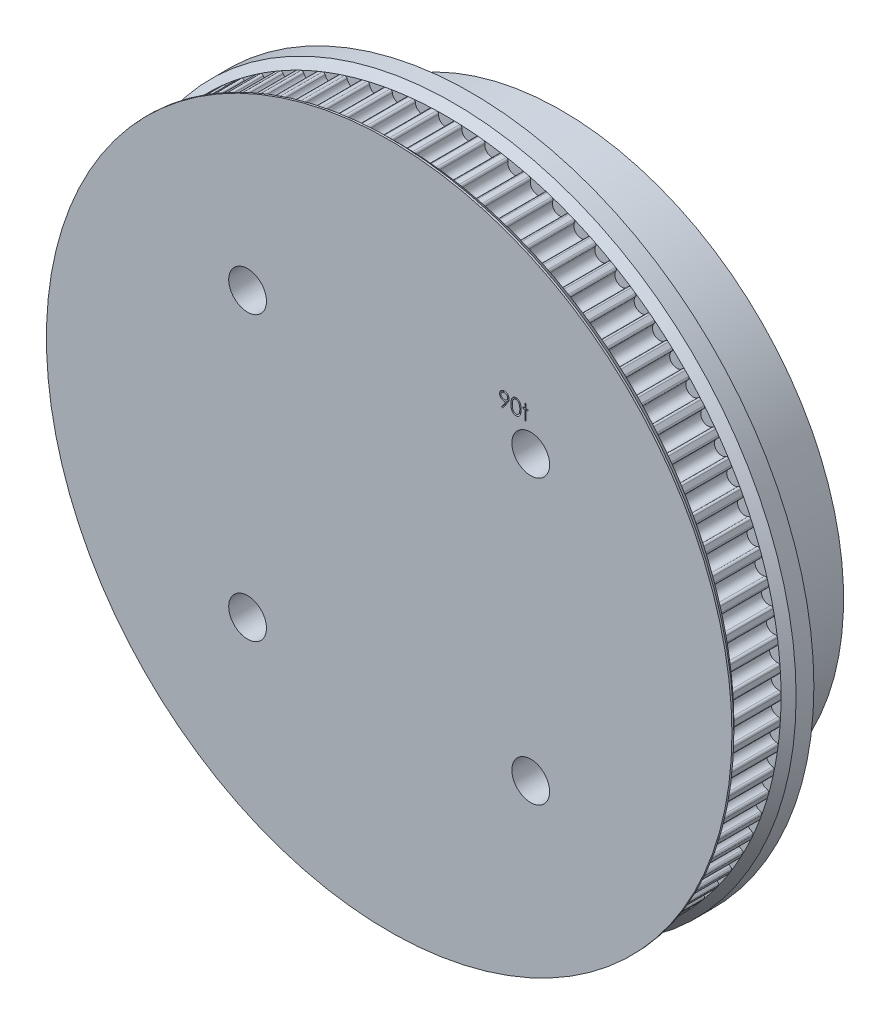
SolidWorks part; units mm, degrees
ref_plane "Front Plane" through (0, 0, 0) normal (0, 0, 1) x (1, 0, 0)
ref_plane "Top Plane" through (0, 0, 0) normal (0, 1, 0) x (1, 0, 0)
ref_plane "Right Plane" through (0, 0, 0) normal (1, 0, 0) x (0, 0, -1)
sketch "Sketch1" plane through (0, 0, 0) normal (0, 0, 1) x (1, 0, 0)
  line L0 (0, 71.6197) -> (0, 0) construction
  line L1 (0, 0) -> (4.9959, 71.4453) construction
  line L2 (0, 70.4947) -> (1.9534, 70.5727) construction
  line L3 (2.9742, 70.537) -> (4.9175, 70.323) construction
  line L4 (1.9534, 70.5727) -> (1.9653, 71.0025) construction
  line L5 (2.9742, 70.537) -> (2.9923, 70.9667) construction
  arc A0 (0, 71.6197) -> (4.9959, 71.4453) centre (0, 0) cw construction
  circle A1 centre (0, 0) radius 71.6197 construction
  circle A2 centre (0, 0) radius 71.0297
  circle A3 centre (0, 0) radius 68.9697
  circle A8 centre (0, 0) radius 72.7697 construction
  circle A9 centre (0, 70.4947) radius 1.525
  circle A10 centre (4.9175, 70.323) radius 1.525
  circle A11 centre (1.9534, 70.5727) radius 0.43
  circle A12 centre (2.9742, 70.537) radius 0.43
  point P18 (0, 68.9697)
  point P19 (4.2572, 15.8881)
  point P20 (4.2572, 15.8881)
  point P21 (1.5238, 70.5555)
  point P23 (3.4016, 70.49)
  dimension "D6" = 3.05
  dimension "D7" = 3.05
  dimension "D8" = 0.86
  dimension "D9" = 0.86
  dimension "D5" = 3.8
  dimension "D2" = 5
  dimension "D3" = 0.59
  dimension "D4" = 2.06
extrude "Boss-Extrude1" add sketch "Sketch1" along normal blind 10 contours A2
extrude "Cut-Extrude1" cut sketch "Sketch1<5>" along normal through all contours A11 A2 A9 | A12 A10 A2 | A9 | A10 region at (3.3605, 70.8449, 0) region at (1.5896, 70.9067, 0)
sketch "Sketch1<5>" plane through (0, 0, 0) normal (0, 0, 1) x (1, 0, 0) same geometry as "Sketch1"
pattern_circular "CirPattern3" count 90 over 360 about axis through (0, 0, 10) along (0, 0, 1) of "Cut-Extrude1"
sketch "Sketch2" plane through (0, 0, 10) normal (0, 0, 1) x (1, 0, 0)
  circle A0 centre (0, 0) radius 72.7697 construction
  arc A81 (-46.5195, 53.0692) -> (-44.1849, 55.0282) centre (-45.3131, 54.0021) ccw
  arc A82 (-46.5195, 53.0692) -> (-44.1849, 55.0282) centre (-45.3131, 54.0021) ccw
  arc A83 (-46.5195, 53.0692) -> (-47.1451, 53.1278) centre (-46.8597, 52.8062) ccw
  arc A84 (-46.5195, 53.0692) -> (-47.1451, 53.1278) centre (-46.8597, 52.8062) ccw
  arc A85 (-47.1451, 53.1278) -> (-47.9088, 52.4402) centre (0, 0) ccw
  arc A86 (-47.1451, 53.1278) -> (-47.9088, 52.4402) centre (0, 0) ccw
  arc A87 (-47.9088, 52.4402) -> (-47.9159, 51.8119) centre (-47.6187, 52.1227) ccw
  arc A88 (-47.9088, 52.4402) -> (-47.9159, 51.8119) centre (-47.6187, 52.1227) ccw
  arc A89 (-50.1081, 49.6949) -> (-47.9159, 51.8119) centre (-48.9698, 50.7097) ccw
  arc A90 (-50.1081, 49.6949) -> (-47.9159, 51.8119) centre (-48.9698, 50.7097) ccw
  arc A91 (-50.1081, 49.6949) -> (-50.7363, 49.7097) centre (-50.4291, 49.4088) ccw
  arc A92 (-50.1081, 49.6949) -> (-50.7363, 49.7097) centre (-50.4291, 49.4088) ccw
  arc A93 (-50.7363, 49.7097) -> (-51.4501, 48.9705) centre (0, 0) ccw
  arc A95 (-50.7363, 49.7097) -> (-51.4501, 48.9705) centre (0, 0) ccw
  arc A97 (-51.4501, 48.9705) -> (-51.4134, 48.3433) centre (-51.1386, 48.674) ccw
  arc A99 (-51.4501, 48.9705) -> (-51.4134, 48.3433) centre (-51.1386, 48.674) ccw
  arc A101 (-53.4526, 46.0785) -> (-51.4134, 48.3433) centre (-52.3878, 47.1702) ccw
  arc A103 (-53.4526, 46.0785) -> (-51.4134, 48.3433) centre (-52.3878, 47.1702) ccw
  arc A105 (-53.4526, 46.0785) -> (-54.0802, 46.0494) centre (-53.7528, 45.7707) ccw
  arc A107 (-53.4526, 46.0785) -> (-54.0802, 46.0494) centre (-53.7528, 45.7707) ccw
  arc A109 (-54.0802, 46.0494) -> (-54.7408, 45.2622) centre (0, 0) ccw
  arc A111 (-54.0802, 46.0494) -> (-54.7408, 45.2622) centre (0, 0) ccw
  arc A112 (-54.7408, 45.2622) -> (-54.6604, 44.6391) centre (-54.4094, 44.9882) ccw
  arc A114 (-54.7408, 45.2622) -> (-54.6604, 44.6391) centre (-54.4094, 44.9882) ccw
  arc A116 (-56.5367, 42.2376) -> (-54.6604, 44.6391) centre (-55.5506, 43.4009) ccw
  arc A118 (-56.5367, 42.2376) -> (-54.6604, 44.6391) centre (-55.5506, 43.4009) ccw
  arc A122 (-56.5367, 42.2376) -> (-57.1607, 42.1648) centre (-56.8147, 41.9096) ccw
  arc A126 (-56.5367, 42.2376) -> (-57.1607, 42.1648) centre (-56.8147, 41.9096) ccw
  arc A130 (-57.1607, 42.1648) -> (-57.7648, 41.3335) centre (0, 0) ccw
  arc A134 (-57.1607, 42.1648) -> (-57.7648, 41.3335) centre (0, 0) ccw
  arc A138 (-57.7648, 41.3335) -> (-57.6411, 40.7174) centre (-57.4151, 41.0832) ccw
  arc A142 (-57.7648, 41.3335) -> (-57.6411, 40.7174) centre (-57.4151, 41.0832) ccw
  arc A146 (-59.3453, 38.1909) -> (-57.6411, 40.7174) centre (-58.4428, 39.4201) ccw
  arc A150 (-59.3453, 38.1909) -> (-57.6411, 40.7174) centre (-58.4428, 39.4201) ccw
  arc A154 (-59.3453, 38.1909) -> (-59.9628, 38.0748) centre (-59.5998, 37.8443) ccw
  arc A158 (-59.3453, 38.1909) -> (-59.9628, 38.0748) centre (-59.5998, 37.8443) ccw
  arc A162 (-59.9628, 38.0748) -> (-60.5073, 37.2033) centre (0, 0) ccw
  arc A166 (-59.9628, 38.0748) -> (-60.5073, 37.2033) centre (0, 0) ccw
  arc A170 (-60.5073, 37.2033) -> (-60.341, 36.5974) centre (-60.141, 36.9781) ccw
  arc A174 (-60.5073, 37.2033) -> (-60.341, 36.5974) centre (-60.141, 36.9781) ccw
  arc A178 (-61.8648, 33.9581) -> (-60.341, 36.5974) centre (-61.0502, 35.2474) ccw
  arc A182 (-61.8648, 33.9581) -> (-60.341, 36.5974) centre (-61.0502, 35.2474) ccw
  arc A186 (-61.8648, 33.9581) -> (-62.4727, 33.7992) centre (-62.0945, 33.5946) ccw
  arc A190 (-61.8648, 33.9581) -> (-62.4727, 33.7992) centre (-62.0945, 33.5946) ccw
  arc A193 (-62.4727, 33.7992) -> (-62.9551, 32.8919) centre (0, 0) ccw
  arc A195 (-62.4727, 33.7992) -> (-62.9551, 32.8919) centre (0, 0) ccw
  arc A197 (-62.9551, 32.8919) -> (-62.7469, 32.2991) centre (-62.574, 32.6928) ccw
  arc A199 (-62.9551, 32.8919) -> (-62.7469, 32.2991) centre (-62.574, 32.6928) ccw
  arc A201 (-64.0829, 29.5599) -> (-62.7469, 32.2991) centre (-63.3602, 30.9029) ccw
  arc A203 (-64.0829, 29.5599) -> (-62.7469, 32.2991) centre (-63.3602, 30.9029) ccw
  arc A205 (-64.0829, 29.5599) -> (-64.6782, 29.359) centre (-64.2867, 29.1813) ccw
  arc A207 (-64.0829, 29.5599) -> (-64.6782, 29.359) centre (-64.2867, 29.1813) ccw
  arc A209 (-64.6782, 29.359) -> (-65.0962, 28.4202) centre (0, 0) ccw
  arc A211 (-64.6782, 29.359) -> (-65.0962, 28.4202) centre (0, 0) ccw
  arc A213 (-65.0962, 28.4202) -> (-64.8471, 27.8434) centre (-64.7021, 28.2482) ccw
  arc A215 (-65.0962, 28.4202) -> (-64.8471, 27.8434) centre (-64.7021, 28.2482) ccw
  arc A217 (-65.9888, 25.0177) -> (-64.8471, 27.8434) centre (-65.3616, 26.4078) ccw
  arc A221 (-65.9888, 25.0177) -> (-64.8471, 27.8434) centre (-65.3616, 26.4078) ccw
  arc A225 (-65.9888, 25.0177) -> (-66.5686, 24.7758) centre (-66.1656, 24.6258) ccw
  arc A229 (-65.9888, 25.0177) -> (-66.5686, 24.7758) centre (-66.1656, 24.6258) ccw
  arc A233 (-66.5686, 24.7758) -> (-66.9201, 23.8101) centre (0, 0) ccw
  arc A241 (-66.5686, 24.7758) -> (-66.9201, 23.8101) centre (0, 0) ccw
  arc A245 (-66.9201, 23.8101) -> (-66.6314, 23.2521) centre (-66.515, 23.666) ccw
  arc A247 (-66.9201, 23.8101) -> (-66.6314, 23.2521) centre (-66.515, 23.666) ccw
  arc A249 (-67.5732, 20.3537) -> (-66.6314, 23.2521) centre (-67.0445, 21.7841) ccw
  arc A251 (-67.5732, 20.3537) -> (-66.6314, 23.2521) centre (-67.0445, 21.7841) ccw
  arc A253 (-67.5732, 20.3537) -> (-68.1347, 20.0718) centre (-67.7223, 19.9503) ccw
  arc A255 (-67.5732, 20.3537) -> (-68.1347, 20.0718) centre (-67.7223, 19.9503) ccw
  arc A257 (-68.1347, 20.0718) -> (-68.418, 19.084) centre (0, 0) ccw
  arc A259 (-68.1347, 20.0718) -> (-68.418, 19.084) centre (0, 0) ccw
  arc A261 (-68.418, 19.084) -> (-68.0911, 18.5475) centre (-68.0038, 18.9685) ccw
  arc A263 (-68.418, 19.084) -> (-68.0911, 18.5475) centre (-68.0038, 18.9685) ccw
  arc A373 (3.4016, 70.49) -> (6.4418, 70.2774) centre (4.9175, 70.323) ccw
  arc A374 (3.4016, 70.49) -> (2.9923, 70.9667) centre (2.9742, 70.537) ccw
  arc A375 (2.9923, 70.9667) -> (1.9653, 71.0025) centre (0, 0) ccw
  arc A376 (1.9653, 71.0025) -> (1.5238, 70.5555) centre (1.9534, 70.5727) ccw
  arc A377 (-1.5238, 70.5555) -> (1.5238, 70.5555) centre (0, 70.4947) ccw
  arc A378 (-1.5238, 70.5555) -> (-1.9653, 71.0025) centre (-1.9534, 70.5727) ccw
  arc A379 (-1.9653, 71.0025) -> (-2.9923, 70.9667) centre (0, 0) ccw
  arc A380 (-2.9923, 70.9667) -> (-3.4016, 70.49) centre (-2.9742, 70.537) ccw
  arc A381 (-6.4418, 70.2774) -> (-3.4016, 70.49) centre (-4.9175, 70.323) ccw
  arc A382 (-6.4418, 70.2774) -> (-6.9134, 70.6925) centre (-6.8716, 70.2645) ccw
  arc A383 (-6.9134, 70.6925) -> (-7.9354, 70.5851) centre (0, 0) ccw
  arc A384 (-7.9354, 70.5851) -> (-8.3105, 70.081) centre (-7.8874, 70.1578) ccw
  arc A385 (-11.3284, 69.6568) -> (-8.3105, 70.081) centre (-9.811, 69.8087) ccw
  arc A386 (-11.3284, 69.6568) -> (-11.8279, 70.038) centre (-11.7563, 69.614) ccw
  arc A387 (-11.8279, 70.038) -> (-12.8399, 69.8596) centre (0, 0) ccw
  arc A388 (-12.8399, 69.8596) -> (-13.1788, 69.3305) centre (-12.7621, 69.4367) ccw
  arc A389 (-16.1598, 68.6969) -> (-13.1788, 69.3305) centre (-14.6567, 68.9542) ccw
  arc A390 (-16.1598, 68.6969) -> (-16.6847, 69.0423) centre (-16.5836, 68.6244) ccw
  arc A391 (-16.6847, 69.0423) -> (-17.6817, 68.7937) centre (0, 0) ccw
  arc A392 (-17.6817, 68.7937) -> (-17.983, 68.2424) centre (-17.5747, 68.3773) ccw
  arc A393 (-20.9125, 67.4023) -> (-17.983, 68.2424) centre (-19.431, 67.7639) ccw
  arc A394 (-20.9125, 67.4023) -> (-21.4602, 67.7103) centre (-21.3302, 67.3004) ccw
  arc A395 (-21.4602, 67.7103) -> (-22.4375, 67.3927) centre (0, 0) ccw
  arc A396 (-22.4375, 67.3927) -> (-22.6995, 66.8217) centre (-22.3016, 66.9848) ccw
  arc A397 (-25.5633, 65.7794) -> (-22.6995, 66.8217) centre (-24.1106, 66.2434) ccw
  arc A398 (-25.5633, 65.7794) -> (-26.1311, 66.0484) centre (-25.9729, 65.6485) ccw
  arc A399 (-26.1311, 66.0484) -> (-27.0839, 65.6634) centre (0, 0) ccw
  arc A400 (-27.0839, 65.6634) -> (-27.3055, 65.0755) centre (-26.9199, 65.2659) ccw
  arc A401 (-30.0896, 63.8359) -> (-27.3055, 65.0755) centre (-28.6728, 64.4001) ccw
  arc A402 (-30.0896, 63.8359) -> (-30.6748, 64.0647) centre (-30.4891, 63.6768) ccw
  arc A403 (-30.6748, 64.0647) -> (-31.5984, 63.6142) centre (0, 0) ccw
  arc A404 (-31.5984, 63.6142) -> (-31.7784, 63.0122) centre (-31.4071, 63.2291) ccw
  arc A405 (-34.4692, 61.5815) -> (-31.7784, 63.0122) centre (-33.0953, 62.2431) ccw
  arc A406 (-34.4692, 61.5815) -> (-35.069, 61.7688) centre (-34.8567, 61.3949) ccw
  arc A407 (-35.069, 61.7688) -> (-35.9589, 61.255) centre (0, 0) ccw
  arc A408 (-35.9589, 61.255) -> (-36.0965, 60.642) centre (-35.7412, 60.8842) ccw
  arc A409 (-38.681, 59.027) -> (-36.0965, 60.642) centre (-37.3565, 59.7829) ccw
  arc A410 (-38.681, 59.027) -> (-39.2923, 59.1721) centre (-39.0544, 58.8139) ccw
  arc A411 (-39.2923, 59.1721) -> (-40.1442, 58.5975) centre (0, 0) ccw
  arc A412 (-40.1442, 58.5975) -> (-40.2387, 57.9763) centre (-39.9012, 58.2427) ccw
  arc A413 (-42.7043, 56.185) -> (-40.2387, 57.9763) centre (-41.4358, 57.0314) ccw
  arc A414 (-42.7043, 56.185) -> (-43.3242, 56.2871) centre (-43.062, 55.9463) ccw
  arc A415 (-43.3242, 56.2871) -> (-44.134, 55.6544) centre (0, 0) ccw
  arc A416 (-44.134, 55.6544) -> (-44.1849, 55.0282) centre (-43.8668, 55.3175) ccw
  arc A649 (3.4016, 70.49) -> (6.4418, 70.2774) centre (4.9175, 70.323) ccw
  arc A650 (3.4016, 70.49) -> (2.9923, 70.9667) centre (2.9742, 70.537) ccw
  arc A651 (2.9923, 70.9667) -> (1.9653, 71.0025) centre (0, 0) ccw
  arc A652 (1.9653, 71.0025) -> (1.5238, 70.5555) centre (1.9534, 70.5727) ccw
  arc A653 (-1.5238, 70.5555) -> (1.5238, 70.5555) centre (0, 70.4947) ccw
  arc A654 (-1.5238, 70.5555) -> (-1.9653, 71.0025) centre (-1.9534, 70.5727) ccw
  arc A655 (-1.9653, 71.0025) -> (-2.9923, 70.9667) centre (0, 0) ccw
  arc A656 (-2.9923, 70.9667) -> (-3.4016, 70.49) centre (-2.9742, 70.537) ccw
  arc A657 (-6.4418, 70.2774) -> (-3.4016, 70.49) centre (-4.9175, 70.323) ccw
  arc A658 (-6.4418, 70.2774) -> (-6.9134, 70.6925) centre (-6.8716, 70.2645) ccw
  arc A659 (-6.9134, 70.6925) -> (-7.9354, 70.5851) centre (0, 0) ccw
  arc A660 (-7.9354, 70.5851) -> (-8.3105, 70.081) centre (-7.8874, 70.1578) ccw
  arc A661 (-11.3284, 69.6568) -> (-8.3105, 70.081) centre (-9.811, 69.8087) ccw
  arc A662 (-11.3284, 69.6568) -> (-11.8279, 70.038) centre (-11.7563, 69.614) ccw
  arc A663 (-11.8279, 70.038) -> (-12.8399, 69.8596) centre (0, 0) ccw
  arc A664 (-12.8399, 69.8596) -> (-13.1788, 69.3305) centre (-12.7621, 69.4367) ccw
  arc A665 (-16.1598, 68.6969) -> (-13.1788, 69.3305) centre (-14.6567, 68.9542) ccw
  arc A666 (-16.1598, 68.6969) -> (-16.6847, 69.0423) centre (-16.5836, 68.6244) ccw
  arc A667 (-16.6847, 69.0423) -> (-17.6817, 68.7937) centre (0, 0) ccw
  arc A668 (-17.6817, 68.7937) -> (-17.983, 68.2424) centre (-17.5747, 68.3773) ccw
  arc A669 (-20.9125, 67.4023) -> (-17.983, 68.2424) centre (-19.431, 67.7639) ccw
  arc A670 (-20.9125, 67.4023) -> (-21.4602, 67.7103) centre (-21.3302, 67.3004) ccw
  arc A671 (-21.4602, 67.7103) -> (-22.4375, 67.3927) centre (0, 0) ccw
  arc A672 (-22.4375, 67.3927) -> (-22.6995, 66.8217) centre (-22.3016, 66.9848) ccw
  arc A673 (-25.5633, 65.7794) -> (-22.6995, 66.8217) centre (-24.1106, 66.2434) ccw
  arc A674 (-25.5633, 65.7794) -> (-26.1311, 66.0484) centre (-25.9729, 65.6485) ccw
  arc A675 (-26.1311, 66.0484) -> (-27.0839, 65.6634) centre (0, 0) ccw
  arc A676 (-27.0839, 65.6634) -> (-27.3055, 65.0755) centre (-26.9199, 65.2659) ccw
  arc A677 (-30.0896, 63.8359) -> (-27.3055, 65.0755) centre (-28.6728, 64.4001) ccw
  arc A678 (-30.0896, 63.8359) -> (-30.6748, 64.0647) centre (-30.4891, 63.6768) ccw
  arc A679 (-30.6748, 64.0647) -> (-31.5984, 63.6142) centre (0, 0) ccw
  arc A680 (-31.5984, 63.6142) -> (-31.7784, 63.0122) centre (-31.4071, 63.2291) ccw
  arc A681 (-34.4692, 61.5815) -> (-31.7784, 63.0122) centre (-33.0953, 62.2431) ccw
  arc A682 (-34.4692, 61.5815) -> (-35.069, 61.7688) centre (-34.8567, 61.3949) ccw
  arc A683 (-35.069, 61.7688) -> (-35.9589, 61.255) centre (0, 0) ccw
  arc A684 (-35.9589, 61.255) -> (-36.0965, 60.642) centre (-35.7412, 60.8842) ccw
  arc A685 (-38.681, 59.027) -> (-36.0965, 60.642) centre (-37.3565, 59.7829) ccw
  arc A686 (-38.681, 59.027) -> (-39.2923, 59.1721) centre (-39.0544, 58.8139) ccw
  arc A687 (-39.2923, 59.1721) -> (-40.1442, 58.5975) centre (0, 0) ccw
  arc A688 (-40.1442, 58.5975) -> (-40.2387, 57.9763) centre (-39.9012, 58.2427) ccw
  arc A689 (-42.7043, 56.185) -> (-40.2387, 57.9763) centre (-41.4358, 57.0314) ccw
  arc A690 (-42.7043, 56.185) -> (-43.3242, 56.2871) centre (-43.062, 55.9463) ccw
  arc A691 (-43.3242, 56.2871) -> (-44.134, 55.6544) centre (0, 0) ccw
  arc A692 (-44.134, 55.6544) -> (-44.1849, 55.0282) centre (-43.8668, 55.3175) ccw
  arc A1359 (-6.9134, -70.6925) -> (-6.4418, -70.2774) centre (-6.8716, -70.2645) ccw
  arc A1361 (-6.9134, -70.6925) -> (-6.4418, -70.2774) centre (-6.8716, -70.2645) ccw
  arc A1363 (-3.4016, -70.49) -> (-6.4418, -70.2774) centre (-4.9175, -70.323) ccw
  arc A1365 (-3.4016, -70.49) -> (-6.4418, -70.2774) centre (-4.9175, -70.323) ccw
  arc A1367 (-3.4016, -70.49) -> (-2.9923, -70.9667) centre (-2.9742, -70.537) ccw
  arc A1369 (-3.4016, -70.49) -> (-2.9923, -70.9667) centre (-2.9742, -70.537) ccw
  arc A1371 (-2.9923, -70.9667) -> (-1.9653, -71.0025) centre (0, 0) ccw
  arc A1373 (-2.9923, -70.9667) -> (-1.9653, -71.0025) centre (0, 0) ccw
  arc A1375 (-1.9653, -71.0025) -> (-1.5238, -70.5555) centre (-1.9534, -70.5727) ccw
  arc A1377 (-1.9653, -71.0025) -> (-1.5238, -70.5555) centre (-1.9534, -70.5727) ccw
  arc A1379 (1.5238, -70.5555) -> (-1.5238, -70.5555) centre (0, -70.4947) ccw
  arc A1381 (1.5238, -70.5555) -> (-1.5238, -70.5555) centre (0, -70.4947) ccw
  arc A1383 (1.5238, -70.5555) -> (1.9653, -71.0025) centre (1.9534, -70.5727) ccw
  arc A1385 (1.5238, -70.5555) -> (1.9653, -71.0025) centre (1.9534, -70.5727) ccw
  arc A1387 (1.9653, -71.0025) -> (2.9923, -70.9667) centre (0, 0) ccw
  arc A1389 (1.9653, -71.0025) -> (2.9923, -70.9667) centre (0, 0) ccw
  arc A1391 (2.9923, -70.9667) -> (3.4016, -70.49) centre (2.9742, -70.537) ccw
  arc A1393 (2.9923, -70.9667) -> (3.4016, -70.49) centre (2.9742, -70.537) ccw
  arc A1395 (6.4418, -70.2774) -> (3.4016, -70.49) centre (4.9175, -70.323) ccw
  arc A1397 (6.4418, -70.2774) -> (3.4016, -70.49) centre (4.9175, -70.323) ccw
  arc A1399 (6.4418, -70.2774) -> (6.9134, -70.6925) centre (6.8716, -70.2645) ccw
  arc A1401 (6.4418, -70.2774) -> (6.9134, -70.6925) centre (6.8716, -70.2645) ccw
  arc A1403 (6.9134, -70.6925) -> (7.9354, -70.5851) centre (0, 0) ccw
  arc A1405 (6.9134, -70.6925) -> (7.9354, -70.5851) centre (0, 0) ccw
  arc A1407 (7.9354, -70.5851) -> (8.3105, -70.081) centre (7.8874, -70.1578) ccw
  arc A1409 (7.9354, -70.5851) -> (8.3105, -70.081) centre (7.8874, -70.1578) ccw
  arc A1411 (11.3284, -69.6568) -> (8.3105, -70.081) centre (9.811, -69.8087) ccw
  arc A1413 (11.3284, -69.6568) -> (8.3105, -70.081) centre (9.811, -69.8087) ccw
  arc A1415 (11.3284, -69.6568) -> (11.8279, -70.038) centre (11.7563, -69.614) ccw
  arc A1417 (11.3284, -69.6568) -> (11.8279, -70.038) centre (11.7563, -69.614) ccw
  arc A1419 (11.8279, -70.038) -> (12.8399, -69.8596) centre (0, 0) ccw
  arc A1421 (11.8279, -70.038) -> (12.8399, -69.8596) centre (0, 0) ccw
  arc A1423 (12.8399, -69.8596) -> (13.1788, -69.3305) centre (12.7621, -69.4367) ccw
  arc A1425 (12.8399, -69.8596) -> (13.1788, -69.3305) centre (12.7621, -69.4367) ccw
  arc A1427 (16.1598, -68.6969) -> (13.1788, -69.3305) centre (14.6567, -68.9542) ccw
  arc A1429 (16.1598, -68.6969) -> (13.1788, -69.3305) centre (14.6567, -68.9542) ccw
  arc A1431 (16.1598, -68.6969) -> (16.6847, -69.0423) centre (16.5836, -68.6244) ccw
  arc A1433 (16.1598, -68.6969) -> (16.6847, -69.0423) centre (16.5836, -68.6244) ccw
  arc A1435 (16.6847, -69.0423) -> (17.6817, -68.7937) centre (0, 0) ccw
  arc A1437 (16.6847, -69.0423) -> (17.6817, -68.7937) centre (0, 0) ccw
  arc A1439 (17.6817, -68.7937) -> (17.983, -68.2424) centre (17.5747, -68.3773) ccw
  arc A1441 (17.6817, -68.7937) -> (17.983, -68.2424) centre (17.5747, -68.3773) ccw
  arc A1443 (20.9125, -67.4023) -> (17.983, -68.2424) centre (19.431, -67.7639) ccw
  arc A1445 (20.9125, -67.4023) -> (17.983, -68.2424) centre (19.431, -67.7639) ccw
  arc A1447 (20.9125, -67.4023) -> (21.4602, -67.7103) centre (21.3302, -67.3004) ccw
  arc A1449 (20.9125, -67.4023) -> (21.4602, -67.7103) centre (21.3302, -67.3004) ccw
  arc A1451 (21.4602, -67.7103) -> (22.4375, -67.3927) centre (0, 0) ccw
  arc A1453 (21.4602, -67.7103) -> (22.4375, -67.3927) centre (0, 0) ccw
  arc A1455 (22.4375, -67.3927) -> (22.6995, -66.8217) centre (22.3016, -66.9848) ccw
  arc A1457 (22.4375, -67.3927) -> (22.6995, -66.8217) centre (22.3016, -66.9848) ccw
  arc A1459 (25.5633, -65.7794) -> (22.6995, -66.8217) centre (24.1106, -66.2434) ccw
  arc A1461 (25.5633, -65.7794) -> (22.6995, -66.8217) centre (24.1106, -66.2434) ccw
  arc A1463 (25.5633, -65.7794) -> (26.1311, -66.0484) centre (25.9729, -65.6485) ccw
  arc A1465 (25.5633, -65.7794) -> (26.1311, -66.0484) centre (25.9729, -65.6485) ccw
  arc A1467 (26.1311, -66.0484) -> (27.0839, -65.6634) centre (0, 0) ccw
  arc A1469 (26.1311, -66.0484) -> (27.0839, -65.6634) centre (0, 0) ccw
  arc A1471 (27.0839, -65.6634) -> (27.3055, -65.0755) centre (26.9199, -65.2659) ccw
  arc A1473 (27.0839, -65.6634) -> (27.3055, -65.0755) centre (26.9199, -65.2659) ccw
  arc A1475 (30.0896, -63.8359) -> (27.3055, -65.0755) centre (28.6728, -64.4001) ccw
  arc A1477 (30.0896, -63.8359) -> (27.3055, -65.0755) centre (28.6728, -64.4001) ccw
  arc A1479 (30.0896, -63.8359) -> (30.6748, -64.0647) centre (30.4891, -63.6768) ccw
  arc A1481 (30.0896, -63.8359) -> (30.6748, -64.0647) centre (30.4891, -63.6768) ccw
  arc A1483 (30.6748, -64.0647) -> (31.5984, -63.6142) centre (0, 0) ccw
  arc A1485 (30.6748, -64.0647) -> (31.5984, -63.6142) centre (0, 0) ccw
  arc A1487 (31.5984, -63.6142) -> (31.7784, -63.0122) centre (31.4071, -63.2291) ccw
  arc A1489 (31.5984, -63.6142) -> (31.7784, -63.0122) centre (31.4071, -63.2291) ccw
  arc A1491 (34.4692, -61.5815) -> (31.7784, -63.0122) centre (33.0953, -62.2431) ccw
  arc A1493 (34.4692, -61.5815) -> (31.7784, -63.0122) centre (33.0953, -62.2431) ccw
  arc A1495 (34.4692, -61.5815) -> (35.069, -61.7688) centre (34.8567, -61.3949) ccw
  arc A1497 (34.4692, -61.5815) -> (35.069, -61.7688) centre (34.8567, -61.3949) ccw
  arc A1499 (35.069, -61.7688) -> (35.9589, -61.255) centre (0, 0) ccw
  arc A1501 (35.069, -61.7688) -> (35.9589, -61.255) centre (0, 0) ccw
  arc A1503 (35.9589, -61.255) -> (36.0965, -60.642) centre (35.7412, -60.8842) ccw
  arc A1505 (35.9589, -61.255) -> (36.0965, -60.642) centre (35.7412, -60.8842) ccw
  arc A1507 (38.681, -59.027) -> (36.0965, -60.642) centre (37.3565, -59.7829) ccw
  arc A1509 (38.681, -59.027) -> (36.0965, -60.642) centre (37.3565, -59.7829) ccw
  arc A1511 (38.681, -59.027) -> (39.2923, -59.1721) centre (39.0544, -58.8139) ccw
  arc A1513 (38.681, -59.027) -> (39.2923, -59.1721) centre (39.0544, -58.8139) ccw
  arc A1515 (39.2923, -59.1721) -> (40.1442, -58.5975) centre (0, 0) ccw
  arc A1517 (39.2923, -59.1721) -> (40.1442, -58.5975) centre (0, 0) ccw
  arc A1519 (40.1442, -58.5975) -> (40.2387, -57.9763) centre (39.9012, -58.2427) ccw
  arc A1521 (40.1442, -58.5975) -> (40.2387, -57.9763) centre (39.9012, -58.2427) ccw
  arc A1523 (42.7043, -56.185) -> (40.2387, -57.9763) centre (41.4358, -57.0314) ccw
  arc A1525 (42.7043, -56.185) -> (40.2387, -57.9763) centre (41.4358, -57.0314) ccw
  arc A1527 (42.7043, -56.185) -> (43.3242, -56.2871) centre (43.062, -55.9463) ccw
  arc A1529 (42.7043, -56.185) -> (43.3242, -56.2871) centre (43.062, -55.9463) ccw
  arc A1531 (43.3242, -56.2871) -> (44.134, -55.6544) centre (0, 0) ccw
  arc A1533 (43.3242, -56.2871) -> (44.134, -55.6544) centre (0, 0) ccw
  arc A1535 (44.134, -55.6544) -> (44.1849, -55.0282) centre (43.8668, -55.3175) ccw
  arc A1537 (44.134, -55.6544) -> (44.1849, -55.0282) centre (43.8668, -55.3175) ccw
  arc A1539 (46.5195, -53.0692) -> (44.1849, -55.0282) centre (45.3131, -54.0021) ccw
  arc A1541 (46.5195, -53.0692) -> (44.1849, -55.0282) centre (45.3131, -54.0021) ccw
  arc A1543 (46.5195, -53.0692) -> (47.1451, -53.1278) centre (46.8597, -52.8062) ccw
  arc A1545 (46.5195, -53.0692) -> (47.1451, -53.1278) centre (46.8597, -52.8062) ccw
  arc A1547 (47.1451, -53.1278) -> (47.9088, -52.4402) centre (0, 0) ccw
  arc A1549 (47.1451, -53.1278) -> (47.9088, -52.4402) centre (0, 0) ccw
  arc A1551 (47.9088, -52.4402) -> (47.9159, -51.8119) centre (47.6187, -52.1227) ccw
  arc A1553 (47.9088, -52.4402) -> (47.9159, -51.8119) centre (47.6187, -52.1227) ccw
  arc A1555 (50.1081, -49.6949) -> (47.9159, -51.8119) centre (48.9698, -50.7097) ccw
  arc A1557 (50.1081, -49.6949) -> (47.9159, -51.8119) centre (48.9698, -50.7097) ccw
  arc A1559 (50.1081, -49.6949) -> (50.7363, -49.7097) centre (50.4291, -49.4088) ccw
  arc A1561 (50.1081, -49.6949) -> (50.7363, -49.7097) centre (50.4291, -49.4088) ccw
  arc A1563 (50.7363, -49.7097) -> (51.4501, -48.9705) centre (0, 0) ccw
  arc A1565 (50.7363, -49.7097) -> (51.4501, -48.9705) centre (0, 0) ccw
  arc A1567 (51.4501, -48.9705) -> (51.4134, -48.3433) centre (51.1386, -48.674) ccw
  arc A1569 (51.4501, -48.9705) -> (51.4134, -48.3433) centre (51.1386, -48.674) ccw
  arc A1571 (53.4526, -46.0785) -> (51.4134, -48.3433) centre (52.3878, -47.1702) ccw
  arc A1573 (53.4526, -46.0785) -> (51.4134, -48.3433) centre (52.3878, -47.1702) ccw
  arc A1575 (53.4526, -46.0785) -> (54.0802, -46.0494) centre (53.7528, -45.7707) ccw
  arc A1577 (53.4526, -46.0785) -> (54.0802, -46.0494) centre (53.7528, -45.7707) ccw
  arc A1579 (54.0802, -46.0494) -> (54.7408, -45.2622) centre (0, 0) ccw
  arc A1581 (54.0802, -46.0494) -> (54.7408, -45.2622) centre (0, 0) ccw
  arc A1583 (54.7408, -45.2622) -> (54.6604, -44.6391) centre (54.4094, -44.9882) ccw
  arc A1585 (54.7408, -45.2622) -> (54.6604, -44.6391) centre (54.4094, -44.9882) ccw
  arc A1587 (56.5367, -42.2376) -> (54.6604, -44.6391) centre (55.5506, -43.4009) ccw
  arc A1589 (56.5367, -42.2376) -> (54.6604, -44.6391) centre (55.5506, -43.4009) ccw
  arc A1591 (56.5367, -42.2376) -> (57.1607, -42.1648) centre (56.8147, -41.9096) ccw
  arc A1593 (56.5367, -42.2376) -> (57.1607, -42.1648) centre (56.8147, -41.9096) ccw
  arc A1595 (57.1607, -42.1648) -> (57.7648, -41.3335) centre (0, 0) ccw
  arc A1596 (57.1607, -42.1648) -> (57.7648, -41.3335) centre (0, 0) ccw
  arc A1597 (57.7648, -41.3335) -> (57.6411, -40.7174) centre (57.4151, -41.0832) ccw
  arc A1598 (57.7648, -41.3335) -> (57.6411, -40.7174) centre (57.4151, -41.0832) ccw
  arc A1599 (59.3453, -38.1909) -> (57.6411, -40.7174) centre (58.4428, -39.4201) ccw
  arc A1600 (59.3453, -38.1909) -> (57.6411, -40.7174) centre (58.4428, -39.4201) ccw
  arc A1601 (59.3453, -38.1909) -> (59.9628, -38.0748) centre (59.5998, -37.8443) ccw
  arc A1602 (59.3453, -38.1909) -> (59.9628, -38.0748) centre (59.5998, -37.8443) ccw
  arc A1603 (59.9628, -38.0748) -> (60.5073, -37.2033) centre (0, 0) ccw
  arc A1604 (59.9628, -38.0748) -> (60.5073, -37.2033) centre (0, 0) ccw
  arc A1605 (60.5073, -37.2033) -> (60.341, -36.5974) centre (60.141, -36.9781) ccw
  arc A1606 (60.5073, -37.2033) -> (60.341, -36.5974) centre (60.141, -36.9781) ccw
  arc A1607 (61.8648, -33.9581) -> (60.341, -36.5974) centre (61.0502, -35.2474) ccw
  arc A1608 (61.8648, -33.9581) -> (60.341, -36.5974) centre (61.0502, -35.2474) ccw
  arc A1609 (61.8648, -33.9581) -> (62.4727, -33.7992) centre (62.0945, -33.5946) ccw
  arc A1610 (61.8648, -33.9581) -> (62.4727, -33.7992) centre (62.0945, -33.5946) ccw
  arc A1611 (62.4727, -33.7992) -> (62.9551, -32.8919) centre (0, 0) ccw
  arc A1612 (62.4727, -33.7992) -> (62.9551, -32.8919) centre (0, 0) ccw
  arc A1613 (62.9551, -32.8919) -> (62.7469, -32.2991) centre (62.574, -32.6928) ccw
  arc A1614 (62.9551, -32.8919) -> (62.7469, -32.2991) centre (62.574, -32.6928) ccw
  arc A1615 (64.0829, -29.5599) -> (62.7469, -32.2991) centre (63.3602, -30.9029) ccw
  arc A1616 (64.0829, -29.5599) -> (62.7469, -32.2991) centre (63.3602, -30.9029) ccw
  arc A1617 (64.0829, -29.5599) -> (64.6782, -29.359) centre (64.2867, -29.1813) ccw
  arc A1618 (64.0829, -29.5599) -> (64.6782, -29.359) centre (64.2867, -29.1813) ccw
  arc A1619 (64.6782, -29.359) -> (65.0962, -28.4202) centre (0, 0) ccw
  arc A1620 (64.6782, -29.359) -> (65.0962, -28.4202) centre (0, 0) ccw
  arc A1621 (65.0962, -28.4202) -> (64.8471, -27.8434) centre (64.7021, -28.2482) ccw
  arc A1622 (65.0962, -28.4202) -> (64.8471, -27.8434) centre (64.7021, -28.2482) ccw
  arc A1623 (65.9888, -25.0177) -> (64.8471, -27.8434) centre (65.3616, -26.4078) ccw
  arc A1624 (65.9888, -25.0177) -> (64.8471, -27.8434) centre (65.3616, -26.4078) ccw
  arc A1625 (65.9888, -25.0177) -> (66.5686, -24.7758) centre (66.1656, -24.6258) ccw
  arc A1626 (65.9888, -25.0177) -> (66.5686, -24.7758) centre (66.1656, -24.6258) ccw
  arc A1627 (66.5686, -24.7758) -> (66.9201, -23.8101) centre (0, 0) ccw
  arc A1628 (66.5686, -24.7758) -> (66.9201, -23.8101) centre (0, 0) ccw
  arc A1629 (66.9201, -23.8101) -> (66.6314, -23.2521) centre (66.515, -23.666) ccw
  arc A1630 (66.9201, -23.8101) -> (66.6314, -23.2521) centre (66.515, -23.666) ccw
  arc A1631 (67.5732, -20.3537) -> (66.6314, -23.2521) centre (67.0445, -21.7841) ccw
  arc A1632 (67.5732, -20.3537) -> (66.6314, -23.2521) centre (67.0445, -21.7841) ccw
  arc A1633 (67.5732, -20.3537) -> (68.1347, -20.0718) centre (67.7223, -19.9503) ccw
  arc A1634 (67.5732, -20.3537) -> (68.1347, -20.0718) centre (67.7223, -19.9503) ccw
  arc A1635 (68.1347, -20.0718) -> (68.418, -19.084) centre (0, 0) ccw
  arc A1636 (68.1347, -20.0718) -> (68.418, -19.084) centre (0, 0) ccw
  arc A1637 (68.418, -19.084) -> (68.0911, -18.5475) centre (68.0038, -18.9685) ccw
  arc A1638 (68.418, -19.084) -> (68.0911, -18.5475) centre (68.0038, -18.9685) ccw
  arc A1639 (68.8284, -15.5904) -> (68.0911, -18.5475) centre (68.4007, -17.0542) ccw
  arc A1640 (68.8284, -15.5904) -> (68.0911, -18.5475) centre (68.4007, -17.0542) ccw
  arc A1641 (68.8284, -15.5904) -> (69.3689, -15.2701) centre (68.949, -15.1777) ccw
  arc A1642 (68.8284, -15.5904) -> (69.3689, -15.2701) centre (68.949, -15.1777) ccw
  arc A1643 (69.3689, -15.2701) -> (69.5826, -14.2649) centre (0, 0) ccw
  arc A1644 (69.3689, -15.2701) -> (69.5826, -14.2649) centre (0, 0) ccw
  arc A1645 (69.5826, -14.2649) -> (69.219, -13.7525) centre (69.1613, -14.1786) ccw
  arc A1646 (69.5826, -14.2649) -> (69.219, -13.7525) centre (69.1613, -14.1786) ccw
  arc A1647 (69.7483, -10.7512) -> (69.219, -13.7525) centre (69.4238, -12.2413) ccw
  arc A1648 (69.7483, -10.7512) -> (69.219, -13.7525) centre (69.4238, -12.2413) ccw
  arc A1649 (69.7483, -10.7512) -> (70.2651, -10.394) centre (69.8397, -10.3311) ccw
  arc A1650 (69.7483, -10.7512) -> (70.2651, -10.394) centre (69.8397, -10.3311) ccw
  arc A1651 (70.2651, -10.394) -> (70.4081, -9.3764) centre (0, 0) ccw
  arc A1652 (70.2651, -10.394) -> (70.4081, -9.3764) centre (0, 0) ccw
  arc A1653 (70.4081, -9.3764) -> (70.0098, -8.8905) centre (69.9819, -9.3196) ccw
  arc A1654 (70.4081, -9.3764) -> (70.0098, -8.8905) centre (69.9819, -9.3196) ccw
  arc A1655 (70.3283, -5.8596) -> (70.0098, -8.8905) centre (70.1085, -7.3687) ccw
  arc A1656 (70.3283, -5.8596) -> (70.0098, -8.8905) centre (70.1085, -7.3687) ccw
  arc A1657 (70.3283, -5.8596) -> (70.819, -5.4672) centre (70.3903, -5.4341) ccw
  arc A1658 (70.3283, -5.8596) -> (70.819, -5.4672) centre (70.3903, -5.4341) ccw
  arc A1659 (70.819, -5.4672) -> (70.8907, -4.4421) centre (0, 0) ccw
  arc A1660 (70.819, -5.4672) -> (70.8907, -4.4421) centre (0, 0) ccw
  arc A1661 (70.8907, -4.4421) -> (70.4594, -3.9852) centre (70.4615, -4.4152) ccw
  arc A1662 (70.8907, -4.4421) -> (70.4594, -3.9852) centre (70.4615, -4.4152) ccw
  arc A1663 (70.5657, -0.9395) -> (70.4594, -3.9852) centre (70.4518, -2.4602) ccw
  arc A1664 (70.5657, -0.9395) -> (70.4594, -3.9852) centre (70.4518, -2.4602) ccw
  arc A1665 (70.5657, -0.9395) -> (71.0279, -0.5138) centre (70.5979, -0.5107) ccw
  arc A1666 (70.5657, -0.9395) -> (71.0279, -0.5138) centre (70.5979, -0.5107) ccw
  arc A1667 (71.0279, -0.5138) -> (71.0279, 0.5138) centre (0, 0) ccw
  arc A1668 (71.0279, -0.5138) -> (71.0279, 0.5138) centre (0, 0) ccw
  arc A1669 (71.0279, 0.5138) -> (70.5657, 0.9395) centre (70.5979, 0.5107) ccw
  arc A1670 (71.0279, 0.5138) -> (70.5657, 0.9395) centre (70.5979, 0.5107) ccw
  arc A1671 (-68.8284, 15.5904) -> (-68.0911, 18.5475) centre (-68.4007, 17.0542) ccw
  arc A1672 (-68.8284, 15.5904) -> (-68.0911, 18.5475) centre (-68.4007, 17.0542) ccw
  arc A1673 (-68.8284, 15.5904) -> (-69.3689, 15.2701) centre (-68.949, 15.1777) ccw
  arc A1674 (-68.8284, 15.5904) -> (-69.3689, 15.2701) centre (-68.949, 15.1777) ccw
  arc A1675 (-69.3689, 15.2701) -> (-69.5826, 14.2649) centre (0, 0) ccw
  arc A1676 (-69.3689, 15.2701) -> (-69.5826, 14.2649) centre (0, 0) ccw
  arc A1677 (-69.5826, 14.2649) -> (-69.219, 13.7525) centre (-69.1613, 14.1786) ccw
  arc A1678 (-69.5826, 14.2649) -> (-69.219, 13.7525) centre (-69.1613, 14.1786) ccw
  arc A1679 (-69.7483, 10.7512) -> (-69.219, 13.7525) centre (-69.4238, 12.2413) ccw
  arc A1680 (-69.7483, 10.7512) -> (-69.219, 13.7525) centre (-69.4238, 12.2413) ccw
  arc A1681 (-69.7483, 10.7512) -> (-70.2651, 10.394) centre (-69.8397, 10.3311) ccw
  arc A1682 (-69.7483, 10.7512) -> (-70.2651, 10.394) centre (-69.8397, 10.3311) ccw
  arc A1683 (-70.2651, 10.394) -> (-70.4081, 9.3764) centre (0, 0) ccw
  arc A1684 (-70.2651, 10.394) -> (-70.4081, 9.3764) centre (0, 0) ccw
  arc A1685 (-70.4081, 9.3764) -> (-70.0098, 8.8905) centre (-69.9819, 9.3196) ccw
  arc A1686 (-70.4081, 9.3764) -> (-70.0098, 8.8905) centre (-69.9819, 9.3196) ccw
  arc A1687 (-70.3283, 5.8596) -> (-70.0098, 8.8905) centre (-70.1085, 7.3687) ccw
  arc A1688 (-70.3283, 5.8596) -> (-70.0098, 8.8905) centre (-70.1085, 7.3687) ccw
  arc A1689 (-70.3283, 5.8596) -> (-70.819, 5.4672) centre (-70.3903, 5.4341) ccw
  arc A1690 (-70.3283, 5.8596) -> (-70.819, 5.4672) centre (-70.3903, 5.4341) ccw
  arc A1691 (-70.819, 5.4672) -> (-70.8907, 4.4421) centre (0, 0) ccw
  arc A1692 (-70.819, 5.4672) -> (-70.8907, 4.4421) centre (0, 0) ccw
  arc A1693 (-70.8907, 4.4421) -> (-70.4594, 3.9852) centre (-70.4615, 4.4152) ccw
  arc A1694 (-70.8907, 4.4421) -> (-70.4594, 3.9852) centre (-70.4615, 4.4152) ccw
  arc A1695 (-70.5657, 0.9395) -> (-70.4594, 3.9852) centre (-70.4518, 2.4602) ccw
  arc A1696 (-70.5657, 0.9395) -> (-70.4594, 3.9852) centre (-70.4518, 2.4602) ccw
  arc A1697 (-70.5657, 0.9395) -> (-71.0279, 0.5138) centre (-70.5979, 0.5107) ccw
  arc A1698 (-70.5657, 0.9395) -> (-71.0279, 0.5138) centre (-70.5979, 0.5107) ccw
  arc A1699 (-71.0279, 0.5138) -> (-71.0279, -0.5138) centre (0, 0) ccw
  arc A1700 (-71.0279, 0.5138) -> (-71.0279, -0.5138) centre (0, 0) ccw
  arc A1701 (-71.0279, -0.5138) -> (-70.5657, -0.9395) centre (-70.5979, -0.5107) ccw
  arc A1702 (-71.0279, -0.5138) -> (-70.5657, -0.9395) centre (-70.5979, -0.5107) ccw
  arc A1703 (-70.4594, -3.9852) -> (-70.5657, -0.9395) centre (-70.4518, -2.4602) ccw
  arc A1704 (-70.4594, -3.9852) -> (-70.5657, -0.9395) centre (-70.4518, -2.4602) ccw
  arc A1705 (-70.4594, -3.9852) -> (-70.8907, -4.4421) centre (-70.4615, -4.4152) ccw
  arc A1706 (-70.4594, -3.9852) -> (-70.8907, -4.4421) centre (-70.4615, -4.4152) ccw
  arc A1707 (-70.8907, -4.4421) -> (-70.819, -5.4672) centre (0, 0) ccw
  arc A1708 (-70.8907, -4.4421) -> (-70.819, -5.4672) centre (0, 0) ccw
  arc A1709 (-70.819, -5.4672) -> (-70.3283, -5.8596) centre (-70.3903, -5.4341) ccw
  arc A1710 (-70.819, -5.4672) -> (-70.3283, -5.8596) centre (-70.3903, -5.4341) ccw
  arc A1711 (-70.0098, -8.8905) -> (-70.3283, -5.8596) centre (-70.1085, -7.3687) ccw
  arc A1712 (-70.0098, -8.8905) -> (-70.3283, -5.8596) centre (-70.1085, -7.3687) ccw
  arc A1713 (-70.0098, -8.8905) -> (-70.4081, -9.3764) centre (-69.9819, -9.3196) ccw
  arc A1714 (-70.0098, -8.8905) -> (-70.4081, -9.3764) centre (-69.9819, -9.3196) ccw
  arc A1715 (-70.4081, -9.3764) -> (-70.2651, -10.394) centre (0, 0) ccw
  arc A1716 (-70.4081, -9.3764) -> (-70.2651, -10.394) centre (0, 0) ccw
  arc A1717 (-70.2651, -10.394) -> (-69.7483, -10.7512) centre (-69.8397, -10.3311) ccw
  arc A1718 (-70.2651, -10.394) -> (-69.7483, -10.7512) centre (-69.8397, -10.3311) ccw
  arc A1719 (-69.219, -13.7525) -> (-69.7483, -10.7512) centre (-69.4238, -12.2413) ccw
  arc A1720 (-69.219, -13.7525) -> (-69.7483, -10.7512) centre (-69.4238, -12.2413) ccw
  arc A1721 (-69.219, -13.7525) -> (-69.5826, -14.2649) centre (-69.1613, -14.1786) ccw
  arc A1722 (-69.219, -13.7525) -> (-69.5826, -14.2649) centre (-69.1613, -14.1786) ccw
  arc A1723 (-69.5826, -14.2649) -> (-69.3689, -15.2701) centre (0, 0) ccw
  arc A1724 (-69.5826, -14.2649) -> (-69.3689, -15.2701) centre (0, 0) ccw
  arc A1725 (-69.3689, -15.2701) -> (-68.8284, -15.5904) centre (-68.949, -15.1777) ccw
  arc A1726 (-69.3689, -15.2701) -> (-68.8284, -15.5904) centre (-68.949, -15.1777) ccw
  arc A1727 (-68.0911, -18.5475) -> (-68.8284, -15.5904) centre (-68.4007, -17.0542) ccw
  arc A1728 (-68.0911, -18.5475) -> (-68.8284, -15.5904) centre (-68.4007, -17.0542) ccw
  arc A1729 (-68.0911, -18.5475) -> (-68.418, -19.084) centre (-68.0038, -18.9685) ccw
  arc A1730 (-68.0911, -18.5475) -> (-68.418, -19.084) centre (-68.0038, -18.9685) ccw
  arc A1731 (-68.418, -19.084) -> (-68.1347, -20.0718) centre (0, 0) ccw
  arc A1732 (-68.418, -19.084) -> (-68.1347, -20.0718) centre (0, 0) ccw
  arc A1733 (-68.1347, -20.0718) -> (-67.5732, -20.3537) centre (-67.7223, -19.9503) ccw
  arc A1734 (-68.1347, -20.0718) -> (-67.5732, -20.3537) centre (-67.7223, -19.9503) ccw
  arc A1735 (-66.6314, -23.2521) -> (-67.5732, -20.3537) centre (-67.0445, -21.7841) ccw
  arc A1736 (-66.6314, -23.2521) -> (-67.5732, -20.3537) centre (-67.0445, -21.7841) ccw
  arc A1737 (-66.6314, -23.2521) -> (-66.9201, -23.8101) centre (-66.515, -23.666) ccw
  arc A1738 (-66.6314, -23.2521) -> (-66.9201, -23.8101) centre (-66.515, -23.666) ccw
  arc A1739 (-66.9201, -23.8101) -> (-66.5686, -24.7758) centre (0, 0) ccw
  arc A1740 (-66.9201, -23.8101) -> (-66.5686, -24.7758) centre (0, 0) ccw
  arc A1741 (-66.5686, -24.7758) -> (-65.9888, -25.0177) centre (-66.1656, -24.6258) ccw
  arc A1742 (-66.5686, -24.7758) -> (-65.9888, -25.0177) centre (-66.1656, -24.6258) ccw
  arc A1743 (-64.8471, -27.8434) -> (-65.9888, -25.0177) centre (-65.3616, -26.4078) ccw
  arc A1744 (-64.8471, -27.8434) -> (-65.9888, -25.0177) centre (-65.3616, -26.4078) ccw
  arc A1745 (-64.8471, -27.8434) -> (-65.0962, -28.4202) centre (-64.7021, -28.2482) ccw
  arc A1746 (-64.8471, -27.8434) -> (-65.0962, -28.4202) centre (-64.7021, -28.2482) ccw
  arc A1747 (-65.0962, -28.4202) -> (-64.6782, -29.359) centre (0, 0) ccw
  arc A1748 (-65.0962, -28.4202) -> (-64.6782, -29.359) centre (0, 0) ccw
  arc A1749 (-64.6782, -29.359) -> (-64.0829, -29.5599) centre (-64.2867, -29.1813) ccw
  arc A1750 (-64.6782, -29.359) -> (-64.0829, -29.5599) centre (-64.2867, -29.1813) ccw
  arc A1751 (-62.7469, -32.2991) -> (-64.0829, -29.5599) centre (-63.3602, -30.9029) ccw
  arc A1752 (-62.7469, -32.2991) -> (-64.0829, -29.5599) centre (-63.3602, -30.9029) ccw
  arc A1753 (-62.7469, -32.2991) -> (-62.9551, -32.8919) centre (-62.574, -32.6928) ccw
  arc A1754 (-62.7469, -32.2991) -> (-62.9551, -32.8919) centre (-62.574, -32.6928) ccw
  arc A1755 (-62.9551, -32.8919) -> (-62.4727, -33.7992) centre (0, 0) ccw
  arc A1756 (-62.9551, -32.8919) -> (-62.4727, -33.7992) centre (0, 0) ccw
  arc A1757 (-62.4727, -33.7992) -> (-61.8648, -33.9581) centre (-62.0945, -33.5946) ccw
  arc A1758 (-62.4727, -33.7992) -> (-61.8648, -33.9581) centre (-62.0945, -33.5946) ccw
  arc A1759 (-60.341, -36.5974) -> (-61.8648, -33.9581) centre (-61.0502, -35.2474) ccw
  arc A1760 (-60.341, -36.5974) -> (-61.8648, -33.9581) centre (-61.0502, -35.2474) ccw
  arc A1761 (-60.341, -36.5974) -> (-60.5073, -37.2033) centre (-60.141, -36.9781) ccw
  arc A1762 (-60.341, -36.5974) -> (-60.5073, -37.2033) centre (-60.141, -36.9781) ccw
  arc A1763 (-60.5073, -37.2033) -> (-59.9628, -38.0748) centre (0, 0) ccw
  arc A1764 (-60.5073, -37.2033) -> (-59.9628, -38.0748) centre (0, 0) ccw
  arc A1765 (-59.9628, -38.0748) -> (-59.3453, -38.1909) centre (-59.5998, -37.8443) ccw
  arc A1766 (-59.9628, -38.0748) -> (-59.3453, -38.1909) centre (-59.5998, -37.8443) ccw
  arc A1767 (-57.6411, -40.7174) -> (-59.3453, -38.1909) centre (-58.4428, -39.4201) ccw
  arc A1768 (-57.6411, -40.7174) -> (-59.3453, -38.1909) centre (-58.4428, -39.4201) ccw
  arc A1769 (-57.6411, -40.7174) -> (-57.7648, -41.3335) centre (-57.4151, -41.0832) ccw
  arc A1770 (-57.6411, -40.7174) -> (-57.7648, -41.3335) centre (-57.4151, -41.0832) ccw
  arc A1771 (-57.7648, -41.3335) -> (-57.1607, -42.1648) centre (0, 0) ccw
  arc A1772 (-57.7648, -41.3335) -> (-57.1607, -42.1648) centre (0, 0) ccw
  arc A1773 (-57.1607, -42.1648) -> (-56.5367, -42.2376) centre (-56.8147, -41.9096) ccw
  arc A1774 (-57.1607, -42.1648) -> (-56.5367, -42.2376) centre (-56.8147, -41.9096) ccw
  arc A1775 (-54.6604, -44.6391) -> (-56.5367, -42.2376) centre (-55.5506, -43.4009) ccw
  arc A1776 (-54.6604, -44.6391) -> (-56.5367, -42.2376) centre (-55.5506, -43.4009) ccw
  arc A1777 (-54.6604, -44.6391) -> (-54.7408, -45.2622) centre (-54.4094, -44.9882) ccw
  arc A1778 (-54.6604, -44.6391) -> (-54.7408, -45.2622) centre (-54.4094, -44.9882) ccw
  arc A1779 (-54.7408, -45.2622) -> (-54.0802, -46.0494) centre (0, 0) ccw
  arc A1780 (-54.7408, -45.2622) -> (-54.0802, -46.0494) centre (0, 0) ccw
  arc A1781 (-54.0802, -46.0494) -> (-53.4526, -46.0785) centre (-53.7528, -45.7707) ccw
  arc A1782 (-54.0802, -46.0494) -> (-53.4526, -46.0785) centre (-53.7528, -45.7707) ccw
  arc A1783 (-51.4134, -48.3433) -> (-53.4526, -46.0785) centre (-52.3878, -47.1702) ccw
  arc A1784 (-51.4134, -48.3433) -> (-53.4526, -46.0785) centre (-52.3878, -47.1702) ccw
  arc A1785 (-51.4134, -48.3433) -> (-51.4501, -48.9705) centre (-51.1386, -48.674) ccw
  arc A1786 (-51.4134, -48.3433) -> (-51.4501, -48.9705) centre (-51.1386, -48.674) ccw
  arc A1787 (-51.4501, -48.9705) -> (-50.7363, -49.7097) centre (0, 0) ccw
  arc A1788 (-51.4501, -48.9705) -> (-50.7363, -49.7097) centre (0, 0) ccw
  arc A1789 (-50.7363, -49.7097) -> (-50.1081, -49.6949) centre (-50.4291, -49.4088) ccw
  arc A1790 (-50.7363, -49.7097) -> (-50.1081, -49.6949) centre (-50.4291, -49.4088) ccw
  arc A1791 (-47.9159, -51.8119) -> (-50.1081, -49.6949) centre (-48.9698, -50.7097) ccw
  arc A1792 (-47.9159, -51.8119) -> (-50.1081, -49.6949) centre (-48.9698, -50.7097) ccw
  arc A1793 (-47.9159, -51.8119) -> (-47.9088, -52.4402) centre (-47.6187, -52.1227) ccw
  arc A1794 (-47.9159, -51.8119) -> (-47.9088, -52.4402) centre (-47.6187, -52.1227) ccw
  arc A1795 (-47.9088, -52.4402) -> (-47.1451, -53.1278) centre (0, 0) ccw
  arc A1796 (-47.9088, -52.4402) -> (-47.1451, -53.1278) centre (0, 0) ccw
  arc A1797 (-47.1451, -53.1278) -> (-46.5195, -53.0692) centre (-46.8597, -52.8062) ccw
  arc A1798 (-47.1451, -53.1278) -> (-46.5195, -53.0692) centre (-46.8597, -52.8062) ccw
  arc A1799 (-44.1849, -55.0282) -> (-46.5195, -53.0692) centre (-45.3131, -54.0021) ccw
  arc A1800 (-44.1849, -55.0282) -> (-46.5195, -53.0692) centre (-45.3131, -54.0021) ccw
  arc A1801 (-44.1849, -55.0282) -> (-44.134, -55.6544) centre (-43.8668, -55.3175) ccw
  arc A1802 (-44.1849, -55.0282) -> (-44.134, -55.6544) centre (-43.8668, -55.3175) ccw
  arc A1803 (-44.134, -55.6544) -> (-43.3242, -56.2871) centre (0, 0) ccw
  arc A1804 (-44.134, -55.6544) -> (-43.3242, -56.2871) centre (0, 0) ccw
  arc A1805 (-43.3242, -56.2871) -> (-42.7043, -56.185) centre (-43.062, -55.9463) ccw
  arc A1806 (-43.3242, -56.2871) -> (-42.7043, -56.185) centre (-43.062, -55.9463) ccw
  arc A1807 (-40.2387, -57.9763) -> (-42.7043, -56.185) centre (-41.4358, -57.0314) ccw
  arc A1808 (-40.2387, -57.9763) -> (-42.7043, -56.185) centre (-41.4358, -57.0314) ccw
  arc A1809 (-40.2387, -57.9763) -> (-40.1442, -58.5975) centre (-39.9012, -58.2427) ccw
  arc A1810 (-40.2387, -57.9763) -> (-40.1442, -58.5975) centre (-39.9012, -58.2427) ccw
  arc A1811 (-40.1442, -58.5975) -> (-39.2923, -59.1721) centre (0, 0) ccw
  arc A1812 (-40.1442, -58.5975) -> (-39.2923, -59.1721) centre (0, 0) ccw
  arc A1813 (-39.2923, -59.1721) -> (-38.681, -59.027) centre (-39.0544, -58.8139) ccw
  arc A1814 (-39.2923, -59.1721) -> (-38.681, -59.027) centre (-39.0544, -58.8139) ccw
  arc A1815 (-36.0965, -60.642) -> (-38.681, -59.027) centre (-37.3565, -59.7829) ccw
  arc A1816 (-36.0965, -60.642) -> (-38.681, -59.027) centre (-37.3565, -59.7829) ccw
  arc A1817 (-36.0965, -60.642) -> (-35.9589, -61.255) centre (-35.7412, -60.8842) ccw
  arc A1818 (-36.0965, -60.642) -> (-35.9589, -61.255) centre (-35.7412, -60.8842) ccw
  arc A1819 (-35.9589, -61.255) -> (-35.069, -61.7688) centre (0, 0) ccw
  arc A1820 (-35.9589, -61.255) -> (-35.069, -61.7688) centre (0, 0) ccw
  arc A1821 (-35.069, -61.7688) -> (-34.4692, -61.5815) centre (-34.8567, -61.3949) ccw
  arc A1822 (-35.069, -61.7688) -> (-34.4692, -61.5815) centre (-34.8567, -61.3949) ccw
  arc A1823 (-31.7784, -63.0122) -> (-34.4692, -61.5815) centre (-33.0953, -62.2431) ccw
  arc A1824 (-31.7784, -63.0122) -> (-34.4692, -61.5815) centre (-33.0953, -62.2431) ccw
  arc A1825 (-31.7784, -63.0122) -> (-31.5984, -63.6142) centre (-31.4071, -63.2291) ccw
  arc A1826 (-31.7784, -63.0122) -> (-31.5984, -63.6142) centre (-31.4071, -63.2291) ccw
  arc A1827 (-31.5984, -63.6142) -> (-30.6748, -64.0647) centre (0, 0) ccw
  arc A1828 (-31.5984, -63.6142) -> (-30.6748, -64.0647) centre (0, 0) ccw
  arc A1829 (-30.6748, -64.0647) -> (-30.0896, -63.8359) centre (-30.4891, -63.6768) ccw
  arc A1830 (-30.6748, -64.0647) -> (-30.0896, -63.8359) centre (-30.4891, -63.6768) ccw
  arc A1831 (-27.3055, -65.0755) -> (-30.0896, -63.8359) centre (-28.6728, -64.4001) ccw
  arc A1832 (-27.3055, -65.0755) -> (-30.0896, -63.8359) centre (-28.6728, -64.4001) ccw
  arc A1833 (-27.3055, -65.0755) -> (-27.0839, -65.6634) centre (-26.9199, -65.2659) ccw
  arc A1834 (-27.3055, -65.0755) -> (-27.0839, -65.6634) centre (-26.9199, -65.2659) ccw
  arc A1835 (-27.0839, -65.6634) -> (-26.1311, -66.0484) centre (0, 0) ccw
  arc A1836 (-27.0839, -65.6634) -> (-26.1311, -66.0484) centre (0, 0) ccw
  arc A1837 (-26.1311, -66.0484) -> (-25.5633, -65.7794) centre (-25.9729, -65.6485) ccw
  arc A1838 (-26.1311, -66.0484) -> (-25.5633, -65.7794) centre (-25.9729, -65.6485) ccw
  arc A1839 (-22.6995, -66.8217) -> (-25.5633, -65.7794) centre (-24.1106, -66.2434) ccw
  arc A1840 (-22.6995, -66.8217) -> (-25.5633, -65.7794) centre (-24.1106, -66.2434) ccw
  arc A1841 (-22.6995, -66.8217) -> (-22.4375, -67.3927) centre (-22.3016, -66.9848) ccw
  arc A1842 (-22.6995, -66.8217) -> (-22.4375, -67.3927) centre (-22.3016, -66.9848) ccw
  arc A1843 (-22.4375, -67.3927) -> (-21.4602, -67.7103) centre (0, 0) ccw
  arc A1844 (-22.4375, -67.3927) -> (-21.4602, -67.7103) centre (0, 0) ccw
  arc A1845 (-21.4602, -67.7103) -> (-20.9125, -67.4023) centre (-21.3302, -67.3004) ccw
  arc A1846 (-21.4602, -67.7103) -> (-20.9125, -67.4023) centre (-21.3302, -67.3004) ccw
  arc A1847 (-17.983, -68.2424) -> (-20.9125, -67.4023) centre (-19.431, -67.7639) ccw
  arc A1848 (-17.983, -68.2424) -> (-20.9125, -67.4023) centre (-19.431, -67.7639) ccw
  arc A1849 (-17.983, -68.2424) -> (-17.6817, -68.7937) centre (-17.5747, -68.3773) ccw
  arc A1850 (-17.983, -68.2424) -> (-17.6817, -68.7937) centre (-17.5747, -68.3773) ccw
  arc A1851 (-17.6817, -68.7937) -> (-16.6847, -69.0423) centre (0, 0) ccw
  arc A1852 (-17.6817, -68.7937) -> (-16.6847, -69.0423) centre (0, 0) ccw
  arc A1853 (-16.6847, -69.0423) -> (-16.1598, -68.6969) centre (-16.5836, -68.6244) ccw
  arc A1854 (-16.6847, -69.0423) -> (-16.1598, -68.6969) centre (-16.5836, -68.6244) ccw
  arc A1855 (-13.1788, -69.3305) -> (-16.1598, -68.6969) centre (-14.6567, -68.9542) ccw
  arc A1856 (-13.1788, -69.3305) -> (-16.1598, -68.6969) centre (-14.6567, -68.9542) ccw
  arc A1857 (-13.1788, -69.3305) -> (-12.8399, -69.8596) centre (-12.7621, -69.4367) ccw
  arc A1858 (-13.1788, -69.3305) -> (-12.8399, -69.8596) centre (-12.7621, -69.4367) ccw
  arc A1859 (-12.8399, -69.8596) -> (-11.8279, -70.038) centre (0, 0) ccw
  arc A1860 (-12.8399, -69.8596) -> (-11.8279, -70.038) centre (0, 0) ccw
  arc A1861 (-11.8279, -70.038) -> (-11.3284, -69.6568) centre (-11.7563, -69.614) ccw
  arc A1862 (-11.8279, -70.038) -> (-11.3284, -69.6568) centre (-11.7563, -69.614) ccw
  arc A1863 (-8.3105, -70.081) -> (-11.3284, -69.6568) centre (-9.811, -69.8087) ccw
  arc A1864 (-8.3105, -70.081) -> (-11.3284, -69.6568) centre (-9.811, -69.8087) ccw
  arc A1865 (-8.3105, -70.081) -> (-7.9354, -70.5851) centre (-7.8874, -70.1578) ccw
  arc A1866 (-8.3105, -70.081) -> (-7.9354, -70.5851) centre (-7.8874, -70.1578) ccw
  arc A1867 (-7.9354, -70.5851) -> (-6.9134, -70.6925) centre (0, 0) ccw
  arc A1868 (-7.9354, -70.5851) -> (-6.9134, -70.6925) centre (0, 0) ccw
  arc A1869 (70.4594, 3.9852) -> (70.5657, 0.9395) centre (70.4518, 2.4602) ccw
  arc A1870 (70.4594, 3.9852) -> (70.5657, 0.9395) centre (70.4518, 2.4602) ccw
  arc A1871 (70.4594, 3.9852) -> (70.8907, 4.4421) centre (70.4615, 4.4152) ccw
  arc A1872 (70.4594, 3.9852) -> (70.8907, 4.4421) centre (70.4615, 4.4152) ccw
  arc A1873 (70.8907, 4.4421) -> (70.819, 5.4672) centre (0, 0) ccw
  arc A1874 (70.8907, 4.4421) -> (70.819, 5.4672) centre (0, 0) ccw
  arc A1875 (70.819, 5.4672) -> (70.3283, 5.8596) centre (70.3903, 5.4341) ccw
  arc A1876 (70.819, 5.4672) -> (70.3283, 5.8596) centre (70.3903, 5.4341) ccw
  arc A1877 (70.0098, 8.8905) -> (70.3283, 5.8596) centre (70.1085, 7.3687) ccw
  arc A1878 (70.0098, 8.8905) -> (70.3283, 5.8596) centre (70.1085, 7.3687) ccw
  arc A1879 (70.0098, 8.8905) -> (70.4081, 9.3764) centre (69.9819, 9.3196) ccw
  arc A1880 (70.0098, 8.8905) -> (70.4081, 9.3764) centre (69.9819, 9.3196) ccw
  arc A1881 (70.4081, 9.3764) -> (70.2651, 10.394) centre (0, 0) ccw
  arc A1882 (70.4081, 9.3764) -> (70.2651, 10.394) centre (0, 0) ccw
  arc A1883 (70.2651, 10.394) -> (69.7483, 10.7512) centre (69.8397, 10.3311) ccw
  arc A1884 (70.2651, 10.394) -> (69.7483, 10.7512) centre (69.8397, 10.3311) ccw
  arc A1885 (69.219, 13.7525) -> (69.7483, 10.7512) centre (69.4238, 12.2413) ccw
  arc A1886 (69.219, 13.7525) -> (69.7483, 10.7512) centre (69.4238, 12.2413) ccw
  arc A1887 (69.219, 13.7525) -> (69.5826, 14.2649) centre (69.1613, 14.1786) ccw
  arc A1888 (69.219, 13.7525) -> (69.5826, 14.2649) centre (69.1613, 14.1786) ccw
  arc A1889 (69.5826, 14.2649) -> (69.3689, 15.2701) centre (0, 0) ccw
  arc A1890 (69.5826, 14.2649) -> (69.3689, 15.2701) centre (0, 0) ccw
  arc A1891 (69.3689, 15.2701) -> (68.8284, 15.5904) centre (68.949, 15.1777) ccw
  arc A1892 (69.3689, 15.2701) -> (68.8284, 15.5904) centre (68.949, 15.1777) ccw
  arc A1893 (68.0911, 18.5475) -> (68.8284, 15.5904) centre (68.4007, 17.0542) ccw
  arc A1894 (68.0911, 18.5475) -> (68.8284, 15.5904) centre (68.4007, 17.0542) ccw
  arc A1895 (68.0911, 18.5475) -> (68.418, 19.084) centre (68.0038, 18.9685) ccw
  arc A1896 (68.0911, 18.5475) -> (68.418, 19.084) centre (68.0038, 18.9685) ccw
  arc A1897 (68.418, 19.084) -> (68.1347, 20.0718) centre (0, 0) ccw
  arc A1898 (68.418, 19.084) -> (68.1347, 20.0718) centre (0, 0) ccw
  arc A1899 (68.1347, 20.0718) -> (67.5732, 20.3537) centre (67.7223, 19.9503) ccw
  arc A1900 (68.1347, 20.0718) -> (67.5732, 20.3537) centre (67.7223, 19.9503) ccw
  arc A1901 (66.6314, 23.2521) -> (67.5732, 20.3537) centre (67.0445, 21.7841) ccw
  arc A1902 (66.6314, 23.2521) -> (67.5732, 20.3537) centre (67.0445, 21.7841) ccw
  arc A1903 (66.6314, 23.2521) -> (66.9201, 23.8101) centre (66.515, 23.666) ccw
  arc A1904 (66.6314, 23.2521) -> (66.9201, 23.8101) centre (66.515, 23.666) ccw
  arc A1905 (66.9201, 23.8101) -> (66.5686, 24.7758) centre (0, 0) ccw
  arc A1906 (66.9201, 23.8101) -> (66.5686, 24.7758) centre (0, 0) ccw
  arc A1907 (66.5686, 24.7758) -> (65.9888, 25.0177) centre (66.1656, 24.6258) ccw
  arc A1908 (66.5686, 24.7758) -> (65.9888, 25.0177) centre (66.1656, 24.6258) ccw
  arc A1909 (64.8471, 27.8434) -> (65.9888, 25.0177) centre (65.3616, 26.4078) ccw
  arc A1910 (64.8471, 27.8434) -> (65.9888, 25.0177) centre (65.3616, 26.4078) ccw
  arc A1911 (64.8471, 27.8434) -> (65.0962, 28.4202) centre (64.7021, 28.2482) ccw
  arc A1912 (64.8471, 27.8434) -> (65.0962, 28.4202) centre (64.7021, 28.2482) ccw
  arc A1913 (65.0962, 28.4202) -> (64.6782, 29.359) centre (0, 0) ccw
  arc A1914 (65.0962, 28.4202) -> (64.6782, 29.359) centre (0, 0) ccw
  arc A1915 (64.6782, 29.359) -> (64.0829, 29.5599) centre (64.2867, 29.1813) ccw
  arc A1916 (64.6782, 29.359) -> (64.0829, 29.5599) centre (64.2867, 29.1813) ccw
  arc A1917 (62.7469, 32.2991) -> (64.0829, 29.5599) centre (63.3602, 30.9029) ccw
  arc A1918 (62.7469, 32.2991) -> (64.0829, 29.5599) centre (63.3602, 30.9029) ccw
  arc A1919 (62.7469, 32.2991) -> (62.9551, 32.8919) centre (62.574, 32.6928) ccw
  arc A1920 (62.7469, 32.2991) -> (62.9551, 32.8919) centre (62.574, 32.6928) ccw
  arc A1921 (62.9551, 32.8919) -> (62.4727, 33.7992) centre (0, 0) ccw
  arc A1922 (62.9551, 32.8919) -> (62.4727, 33.7992) centre (0, 0) ccw
  arc A1923 (62.4727, 33.7992) -> (61.8648, 33.9581) centre (62.0945, 33.5946) ccw
  arc A1924 (62.4727, 33.7992) -> (61.8648, 33.9581) centre (62.0945, 33.5946) ccw
  arc A1925 (60.341, 36.5974) -> (61.8648, 33.9581) centre (61.0502, 35.2474) ccw
  arc A1926 (60.341, 36.5974) -> (61.8648, 33.9581) centre (61.0502, 35.2474) ccw
  arc A1927 (60.341, 36.5974) -> (60.5073, 37.2033) centre (60.141, 36.9781) ccw
  arc A1928 (60.341, 36.5974) -> (60.5073, 37.2033) centre (60.141, 36.9781) ccw
  arc A1929 (60.5073, 37.2033) -> (59.9628, 38.0748) centre (0, 0) ccw
  arc A1930 (60.5073, 37.2033) -> (59.9628, 38.0748) centre (0, 0) ccw
  arc A1931 (59.9628, 38.0748) -> (59.3453, 38.1909) centre (59.5998, 37.8443) ccw
  arc A1932 (59.9628, 38.0748) -> (59.3453, 38.1909) centre (59.5998, 37.8443) ccw
  arc A1933 (57.6411, 40.7174) -> (59.3453, 38.1909) centre (58.4428, 39.4201) ccw
  arc A1934 (57.6411, 40.7174) -> (59.3453, 38.1909) centre (58.4428, 39.4201) ccw
  arc A1935 (57.6411, 40.7174) -> (57.7648, 41.3335) centre (57.4151, 41.0832) ccw
  arc A1936 (57.6411, 40.7174) -> (57.7648, 41.3335) centre (57.4151, 41.0832) ccw
  arc A1937 (57.7648, 41.3335) -> (57.1607, 42.1648) centre (0, 0) ccw
  arc A1938 (57.7648, 41.3335) -> (57.1607, 42.1648) centre (0, 0) ccw
  arc A1939 (57.1607, 42.1648) -> (56.5367, 42.2376) centre (56.8147, 41.9096) ccw
  arc A1940 (57.1607, 42.1648) -> (56.5367, 42.2376) centre (56.8147, 41.9096) ccw
  arc A1941 (54.6604, 44.6391) -> (56.5367, 42.2376) centre (55.5506, 43.4009) ccw
  arc A1942 (54.6604, 44.6391) -> (56.5367, 42.2376) centre (55.5506, 43.4009) ccw
  arc A1943 (54.6604, 44.6391) -> (54.7408, 45.2622) centre (54.4094, 44.9882) ccw
  arc A1944 (54.6604, 44.6391) -> (54.7408, 45.2622) centre (54.4094, 44.9882) ccw
  arc A1945 (54.7408, 45.2622) -> (54.0802, 46.0494) centre (0, 0) ccw
  arc A1946 (54.7408, 45.2622) -> (54.0802, 46.0494) centre (0, 0) ccw
  arc A1947 (54.0802, 46.0494) -> (53.4526, 46.0785) centre (53.7528, 45.7707) ccw
  arc A1948 (54.0802, 46.0494) -> (53.4526, 46.0785) centre (53.7528, 45.7707) ccw
  arc A1949 (51.4134, 48.3433) -> (53.4526, 46.0785) centre (52.3878, 47.1702) ccw
  arc A1950 (51.4134, 48.3433) -> (53.4526, 46.0785) centre (52.3878, 47.1702) ccw
  arc A1951 (51.4134, 48.3433) -> (51.4501, 48.9705) centre (51.1386, 48.674) ccw
  arc A1952 (51.4134, 48.3433) -> (51.4501, 48.9705) centre (51.1386, 48.674) ccw
  arc A1953 (51.4501, 48.9705) -> (50.7363, 49.7097) centre (0, 0) ccw
  arc A1954 (51.4501, 48.9705) -> (50.7363, 49.7097) centre (0, 0) ccw
  arc A1955 (50.7363, 49.7097) -> (50.1081, 49.6949) centre (50.4291, 49.4088) ccw
  arc A1956 (50.7363, 49.7097) -> (50.1081, 49.6949) centre (50.4291, 49.4088) ccw
  arc A1957 (47.9159, 51.8119) -> (50.1081, 49.6949) centre (48.9698, 50.7097) ccw
  arc A1958 (47.9159, 51.8119) -> (50.1081, 49.6949) centre (48.9698, 50.7097) ccw
  arc A1959 (47.9159, 51.8119) -> (47.9088, 52.4402) centre (47.6187, 52.1227) ccw
  arc A1960 (47.9159, 51.8119) -> (47.9088, 52.4402) centre (47.6187, 52.1227) ccw
  arc A1961 (47.9088, 52.4402) -> (47.1451, 53.1278) centre (0, 0) ccw
  arc A1962 (47.9088, 52.4402) -> (47.1451, 53.1278) centre (0, 0) ccw
  arc A1963 (47.1451, 53.1278) -> (46.5195, 53.0692) centre (46.8597, 52.8062) ccw
  arc A1964 (47.1451, 53.1278) -> (46.5195, 53.0692) centre (46.8597, 52.8062) ccw
  arc A1965 (44.1849, 55.0282) -> (46.5195, 53.0692) centre (45.3131, 54.0021) ccw
  arc A1966 (44.1849, 55.0282) -> (46.5195, 53.0692) centre (45.3131, 54.0021) ccw
  arc A1967 (44.1849, 55.0282) -> (44.134, 55.6544) centre (43.8668, 55.3175) ccw
  arc A1968 (44.1849, 55.0282) -> (44.134, 55.6544) centre (43.8668, 55.3175) ccw
  arc A1969 (44.134, 55.6544) -> (43.3242, 56.2871) centre (0, 0) ccw
  arc A1970 (44.134, 55.6544) -> (43.3242, 56.2871) centre (0, 0) ccw
  arc A1971 (43.3242, 56.2871) -> (42.7043, 56.185) centre (43.062, 55.9463) ccw
  arc A1972 (43.3242, 56.2871) -> (42.7043, 56.185) centre (43.062, 55.9463) ccw
  arc A1973 (40.2387, 57.9763) -> (42.7043, 56.185) centre (41.4358, 57.0314) ccw
  arc A1974 (40.2387, 57.9763) -> (42.7043, 56.185) centre (41.4358, 57.0314) ccw
  arc A1975 (40.2387, 57.9763) -> (40.1442, 58.5975) centre (39.9012, 58.2427) ccw
  arc A1976 (40.2387, 57.9763) -> (40.1442, 58.5975) centre (39.9012, 58.2427) ccw
  arc A1977 (40.1442, 58.5975) -> (39.2923, 59.1721) centre (0, 0) ccw
  arc A1978 (40.1442, 58.5975) -> (39.2923, 59.1721) centre (0, 0) ccw
  arc A1979 (39.2923, 59.1721) -> (38.681, 59.027) centre (39.0544, 58.8139) ccw
  arc A1980 (39.2923, 59.1721) -> (38.681, 59.027) centre (39.0544, 58.8139) ccw
  arc A1981 (36.0965, 60.642) -> (38.681, 59.027) centre (37.3565, 59.7829) ccw
  arc A1982 (36.0965, 60.642) -> (38.681, 59.027) centre (37.3565, 59.7829) ccw
  arc A1983 (36.0965, 60.642) -> (35.9589, 61.255) centre (35.7412, 60.8842) ccw
  arc A1984 (36.0965, 60.642) -> (35.9589, 61.255) centre (35.7412, 60.8842) ccw
  arc A1985 (35.9589, 61.255) -> (35.069, 61.7688) centre (0, 0) ccw
  arc A1986 (35.9589, 61.255) -> (35.069, 61.7688) centre (0, 0) ccw
  arc A1987 (35.069, 61.7688) -> (34.4692, 61.5815) centre (34.8567, 61.3949) ccw
  arc A1988 (35.069, 61.7688) -> (34.4692, 61.5815) centre (34.8567, 61.3949) ccw
  arc A1989 (31.7784, 63.0122) -> (34.4692, 61.5815) centre (33.0953, 62.2431) ccw
  arc A1990 (31.7784, 63.0122) -> (34.4692, 61.5815) centre (33.0953, 62.2431) ccw
  arc A1991 (31.7784, 63.0122) -> (31.5984, 63.6142) centre (31.4071, 63.2291) ccw
  arc A1992 (31.7784, 63.0122) -> (31.5984, 63.6142) centre (31.4071, 63.2291) ccw
  arc A1993 (31.5984, 63.6142) -> (30.6748, 64.0647) centre (0, 0) ccw
  arc A1994 (31.5984, 63.6142) -> (30.6748, 64.0647) centre (0, 0) ccw
  arc A1995 (30.6748, 64.0647) -> (30.0896, 63.8359) centre (30.4891, 63.6768) ccw
  arc A1996 (30.6748, 64.0647) -> (30.0896, 63.8359) centre (30.4891, 63.6768) ccw
  arc A1997 (27.3055, 65.0755) -> (30.0896, 63.8359) centre (28.6728, 64.4001) ccw
  arc A1998 (27.3055, 65.0755) -> (30.0896, 63.8359) centre (28.6728, 64.4001) ccw
  arc A1999 (27.3055, 65.0755) -> (27.0839, 65.6634) centre (26.9199, 65.2659) ccw
  arc A2000 (27.3055, 65.0755) -> (27.0839, 65.6634) centre (26.9199, 65.2659) ccw
  arc A2001 (27.0839, 65.6634) -> (26.1311, 66.0484) centre (0, 0) ccw
  arc A2002 (27.0839, 65.6634) -> (26.1311, 66.0484) centre (0, 0) ccw
  arc A2003 (26.1311, 66.0484) -> (25.5633, 65.7794) centre (25.9729, 65.6485) ccw
  arc A2004 (26.1311, 66.0484) -> (25.5633, 65.7794) centre (25.9729, 65.6485) ccw
  arc A2005 (22.6995, 66.8217) -> (25.5633, 65.7794) centre (24.1106, 66.2434) ccw
  arc A2006 (22.6995, 66.8217) -> (25.5633, 65.7794) centre (24.1106, 66.2434) ccw
  arc A2007 (22.6995, 66.8217) -> (22.4375, 67.3927) centre (22.3016, 66.9848) ccw
  arc A2008 (22.6995, 66.8217) -> (22.4375, 67.3927) centre (22.3016, 66.9848) ccw
  arc A2009 (22.4375, 67.3927) -> (21.4602, 67.7103) centre (0, 0) ccw
  arc A2010 (22.4375, 67.3927) -> (21.4602, 67.7103) centre (0, 0) ccw
  arc A2011 (21.4602, 67.7103) -> (20.9125, 67.4023) centre (21.3302, 67.3004) ccw
  arc A2012 (21.4602, 67.7103) -> (20.9125, 67.4023) centre (21.3302, 67.3004) ccw
  arc A2013 (17.983, 68.2424) -> (20.9125, 67.4023) centre (19.431, 67.7639) ccw
  arc A2014 (17.983, 68.2424) -> (20.9125, 67.4023) centre (19.431, 67.7639) ccw
  arc A2015 (17.983, 68.2424) -> (17.6817, 68.7937) centre (17.5747, 68.3773) ccw
  arc A2016 (17.983, 68.2424) -> (17.6817, 68.7937) centre (17.5747, 68.3773) ccw
  arc A2017 (17.6817, 68.7937) -> (16.6847, 69.0423) centre (0, 0) ccw
  arc A2018 (17.6817, 68.7937) -> (16.6847, 69.0423) centre (0, 0) ccw
  arc A2019 (16.6847, 69.0423) -> (16.1598, 68.6969) centre (16.5836, 68.6244) ccw
  arc A2020 (16.6847, 69.0423) -> (16.1598, 68.6969) centre (16.5836, 68.6244) ccw
  arc A2021 (13.1788, 69.3305) -> (16.1598, 68.6969) centre (14.6567, 68.9542) ccw
  arc A2022 (13.1788, 69.3305) -> (16.1598, 68.6969) centre (14.6567, 68.9542) ccw
  arc A2023 (13.1788, 69.3305) -> (12.8399, 69.8596) centre (12.7621, 69.4367) ccw
  arc A2024 (13.1788, 69.3305) -> (12.8399, 69.8596) centre (12.7621, 69.4367) ccw
  arc A2025 (12.8399, 69.8596) -> (11.8279, 70.038) centre (0, 0) ccw
  arc A2026 (12.8399, 69.8596) -> (11.8279, 70.038) centre (0, 0) ccw
  arc A2027 (11.8279, 70.038) -> (11.3284, 69.6568) centre (11.7563, 69.614) ccw
  arc A2028 (11.8279, 70.038) -> (11.3284, 69.6568) centre (11.7563, 69.614) ccw
  arc A2029 (8.3105, 70.081) -> (11.3284, 69.6568) centre (9.811, 69.8087) ccw
  arc A2030 (8.3105, 70.081) -> (11.3284, 69.6568) centre (9.811, 69.8087) ccw
  arc A2031 (8.3105, 70.081) -> (7.9354, 70.5851) centre (7.8874, 70.1578) ccw
  arc A2032 (8.3105, 70.081) -> (7.9354, 70.5851) centre (7.8874, 70.1578) ccw
  arc A2033 (7.9354, 70.5851) -> (6.9134, 70.6925) centre (0, 0) ccw
  arc A2034 (7.9354, 70.5851) -> (6.9134, 70.6925) centre (0, 0) ccw
  arc A2035 (6.9134, 70.6925) -> (6.4418, 70.2774) centre (6.8716, 70.2645) ccw
  arc A2036 (6.9134, 70.6925) -> (6.4418, 70.2774) centre (6.8716, 70.2645) ccw
  point P0 (0.0074, 23.4631)
  point P4 (0.0074, 23.4631)
  point P7 (0, 72.7697)
  point P10 (0, 72.7697)
  point P19 (0, 72.7697)
  point P22 (0, 72.7697)
  point P25 (1.6534, 72.7509)
  dimension "D1" = 0
sketch "Sketch3" plane through (0, 0, 0) normal (0, 0, -1) x (-1, 0, 0)
  line L1 (2.5434, -1.3654) -> (2.4542, 1.5199)
  line L2 (2.4542, 1.5199) -> (-0.0892, 2.8854)
  line L3 (-0.0892, 2.8854) -> (-2.5434, 1.3654)
  line L4 (-2.5434, 1.3654) -> (-2.4542, -1.5199)
  line L5 (-2.4542, -1.5199) -> (0.0892, -2.8854)
  line L6 (0.0892, -2.8854) -> (2.5434, -1.3654)
  circle A0 centre (0, 0) radius 2.5 construction
  point P0 (0, 0)
  dimension "D1" = 5
extrude "Cut-Extrude2" [suppressed] cut sketch "Sketch3" against normal through all both and the other way through all
sketch "Sketch5" plane through (0, 0, 0) normal (1, 0, 0) x (0, 0, -1)
  line L1 (0, 0) -> (1.6, 0)
  line L2 (0, 0) -> (0, 71.0297)
  line L3 (0, 71.0297) -> (1.6, 71.0297)
  line L4 (1.6, 0) -> (1.6, 71.0297)
  line L6 (0, 71.0297) -> (1.6, 72.6297)
  line L7 (1.6, 0) -> (2, 0)
  line L8 (1.6, 0) -> (1.6, 72.6297)
  line L9 (1.6, 72.6297) -> (2, 72.6297)
  line L10 (2, 0) -> (2, 72.6297)
  dimension "D1" = 71.0297
  dimension "D3" = 2
  dimension "D4" = 45
  dimension "D2" = 0.4
revolve "Revolve1" add sketch "Sketch5" angle 360 about L7 region at (0, 35.5149, -0.8) region at (0, 36.3149, -1.8) region at (0, 71.5631, -1.0667)
ref_plane "Plane1" through (0, 0, 5) normal (0, 0, 1) x (1, 0, 0)
mirror "Mirror1" about plane through (0, 0, 5) normal (0, 0, 1) of "Revolve1"
sketch "Sketch9" plane through (0, 0, 12) normal (0, 0, 1) x (1, 0, 0)
  text T0 "90t\r\n" font "Century Gothic" height 3.175
extrude "Cut-Extrude5" cut sketch "Sketch9" against normal blind 1
sketch "Sketch10" plane through (0, 0, -2) normal (0, 0, -1) x (-1, 0, 0)
  circle A1 centre (0, 0) radius 72.6297
  circle A2 centre (0, 0) radius 72.6297
  dimension "D1" = 0
extrude "Boss-Extrude3" add sketch "Sketch10" along normal blind 3.365
sketch "Sketch11" plane through (0, 0, -5.365) normal (0, 0, -1) x (-1, 0, 0)
  circle A0 centre (0, 0) radius 59.75
  dimension "D1" = 119.5
extrude "Boss-Extrude4" add sketch "Sketch11" along normal blind 19.175
sketch "Sketch12" plane through (0, 0, 12) normal (0, 0, 1) x (1, 0, 0)
  line L0 (0, 0) -> (0, 47.3377) construction
  line L1 (-30, -30) -> (30, -30) construction
  line L2 (-30, -30) -> (-30, 30) construction
  line L3 (-30, 30) -> (30, 30) construction
  line L4 (30, -30) -> (30, 30) construction
  line L5 (-30, -30) -> (30, 30) construction
  line L6 (-30, 30) -> (30, -30) construction
  line L7 (0, 0) -> (35.5998, 0) construction
  circle A0 centre (-30, 30) radius 2.15
  circle A1 centre (30, 30) radius 2.15
  circle A2 centre (30, -30) radius 2.15
  circle A3 centre (-30, -30) radius 2.15
  circle A4 centre (0, 0) radius 59.75 construction
  point P0 (0, 0)
  dimension "D3" = 4.3
  dimension "D4" = 119.5
  dimension "D1" = 60
  dimension "D2" = 60
extrude "Cut-Extrude6" cut sketch "Sketch12" against normal through all
sketch "Sketch13" plane through (0, 0, 12) normal (0, 0, 1) x (1, 0, 0)
  line L0 (0, 0) -> (0, 51.73) construction
  line L1 (0, 0) -> (44.2598, 0) construction
  circle A0 centre (-30, 30) radius 4
  circle A1 centre (30, 30) radius 4
  circle A2 centre (30, -30) radius 4
  circle A3 centre (-30, -30) radius 4
  dimension "D1" = 8
extrude "Cut-Extrude7" cut sketch "Sketch13" against normal blind 10
equation "\"n\"= 90"
equation "\"D1@Sketch1\"=360/\"n\""
equation "\"D1@CirPattern3\"=\"n\""
equation "\"Width\"= 10"
equation "\"D1@Boss-Extrude1\"=\"Width\""
equation "\"D1@Sketch5\"=(\"n\"*5/pi-0.59*2)/2"
